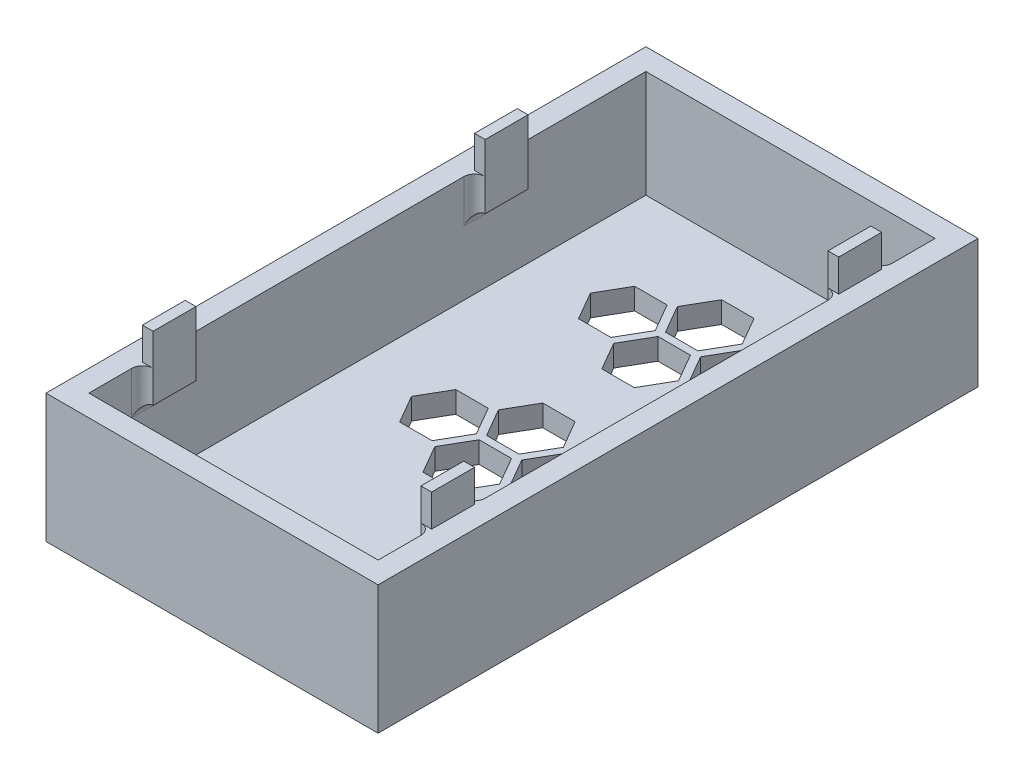
SolidWorks part; units mm, degrees
ref_plane "Plan de face" through (0, 0, 0) normal (0, 0, 1) x (1, 0, 0)
ref_plane "Plan de dessus" through (0, 0, 0) normal (0, 1, 0) x (1, 0, 0)
ref_plane "Plan de droite" through (0, 0, 0) normal (1, 0, 0) x (0, 0, -1)
sketch "Esquisse1" plane through (0, 0, 0) normal (0, 1, 0) x (1, 0, 0)
  line L1 (0, 0) -> (31, 0)
  line L2 (0, 0) -> (0, 56)
  line L3 (0, 56) -> (31, 56)
  line L4 (31, 0) -> (31, 56)
  dimension "D1" = 31
  dimension "D2" = 56
extrude "Boss.-Extru.1" add sketch "Esquisse1" along normal blind 2
sketch "Esquisse2" plane through (0, 2, 0) normal (0, 1, 0) x (1, 0, 0)
  line L0 (16734.8175, -28935.5853) -> (16735.4237, -28935.2353) construction
  line L1 (11.7493, 46.3154) -> (12.3555, 46.6654) construction
  line L2 (13.3806, 43.4899) -> (11.8674, 46.1109)
  line L3 (18.3759, 44.8002) -> (17.7698, 45.1504) construction
  line L4 (15.5, 43.1399) -> (15.5, 43.8399) construction
  line L5 (31, 56) -> (0, 56) construction
  line L6 (13.3806, 26.793) -> (11.8674, 29.4139)
  line L7 (13.2302, 41.8295) -> (12.624, 42.1795) construction
  line L8 (11.8674, 46.1109) -> (8.841, 46.1109)
  line L9 (8.841, 46.1109) -> (7.3278, 43.4899)
  line L10 (7.3278, 43.4899) -> (8.841, 40.869)
  line L11 (8.841, 40.869) -> (11.8674, 40.869)
  line L12 (11.8674, 40.869) -> (13.3806, 43.4899)
  line L13 (18.5264, 46.4609) -> (17.0132, 49.0818)
  line L14 (17.0132, 49.0818) -> (13.9868, 49.0818)
  line L15 (13.9868, 49.0818) -> (12.4736, 46.4609)
  line L16 (12.4736, 46.4609) -> (13.9868, 43.8399)
  line L17 (13.9868, 43.8399) -> (17.0132, 43.8399)
  line L18 (17.0132, 43.8399) -> (18.5264, 46.4609)
  line L19 (18.5264, 40.519) -> (17.0132, 43.1399)
  line L20 (17.0132, 43.1399) -> (13.9868, 43.1399)
  line L21 (13.9868, 43.1399) -> (12.4736, 40.519)
  line L22 (12.4736, 40.519) -> (13.9868, 37.8981)
  line L23 (13.9868, 37.8981) -> (17.0132, 37.8981)
  line L24 (17.0132, 37.8981) -> (18.5264, 40.519)
  line L25 (23.6722, 43.4902) -> (22.1588, 46.111)
  line L26 (22.1588, 46.111) -> (19.1324, 46.1107)
  line L27 (19.1324, 46.1107) -> (17.6194, 43.4897)
  line L28 (17.6194, 43.4897) -> (19.1329, 40.8689)
  line L29 (19.1329, 40.8689) -> (22.1593, 40.8691)
  line L30 (22.1593, 40.8691) -> (23.6722, 43.4902)
  line L31 (17.7698, 41.8295) -> (18.3761, 42.1793) construction
  line L32 (18.3759, 28.1032) -> (17.7698, 28.4534) construction
  line L33 (15.5, 26.443) -> (15.5, 27.143) construction
  line L34 (13.2302, 25.1325) -> (12.624, 25.4825) construction
  line L35 (11.8674, 29.4139) -> (8.841, 29.4139)
  line L36 (8.841, 29.4139) -> (7.3278, 26.793)
  line L37 (7.3278, 26.793) -> (8.841, 24.172)
  line L38 (8.841, 24.172) -> (11.8674, 24.172)
  line L39 (11.8674, 24.172) -> (13.3806, 26.793)
  line L40 (18.5264, 29.7639) -> (17.0132, 32.3848)
  line L41 (17.0132, 32.3848) -> (13.9868, 32.3848)
  line L42 (13.9868, 32.3848) -> (12.4736, 29.7639)
  line L43 (12.4736, 29.7639) -> (13.9868, 27.143)
  line L44 (13.9868, 27.143) -> (17.0132, 27.143)
  line L45 (17.0132, 27.143) -> (18.5264, 29.7639)
  line L46 (18.5264, 23.822) -> (17.0132, 26.443)
  line L47 (17.0132, 26.443) -> (13.9868, 26.443)
  line L48 (13.9868, 26.443) -> (12.4736, 23.822)
  line L49 (12.4736, 23.822) -> (13.9868, 21.2011)
  line L50 (13.9868, 21.2011) -> (17.0132, 21.2011)
  line L51 (17.0132, 21.2011) -> (18.5264, 23.822)
  line L52 (23.6722, 26.7932) -> (22.1588, 29.414)
  line L53 (22.1588, 29.414) -> (19.1324, 29.4138)
  line L54 (19.1324, 29.4138) -> (17.6194, 26.7927)
  line L55 (17.6194, 26.7927) -> (19.1329, 24.1719)
  line L56 (19.1329, 24.1719) -> (22.1593, 24.1722)
  line L57 (22.1593, 24.1722) -> (23.6722, 26.7932)
  line L58 (17.7698, 25.1325) -> (18.3761, 25.4823) construction
  circle A8 centre (10.3542, 43.4899) radius 2.6209 construction
  circle A9 centre (15.5, 46.4609) radius 2.6209 construction
  circle A10 centre (15.5, 40.519) radius 2.6209 construction
  circle A11 centre (20.6458, 43.4899) radius 2.6209 construction
  circle A12 centre (10.3981, 26.7169) radius 2.6209 construction
  circle A13 centre (15.5, 29.7639) radius 2.6209 construction
  circle A14 centre (15.5, 23.822) radius 2.6209 construction
  circle A15 centre (20.6897, 26.7169) radius 2.6209 construction
  point P19 (15.5, 56)
  point P92 (15.5, 32.3848)
  dimension "D1" = 0.7
  dimension "D2" = 0.7
extrude "Enlèv. mat.-Extru.1" cut sketch "Esquisse2" against normal through all
sketch "Esquisse6" plane through (0, 2, 0) normal (0, 1, 0) x (1, 0, 0)
  line L1 (0, 56) -> (31, 56)
  line L2 (0, 56) -> (0, 0)
  line L3 (0, 0) -> (31, 0)
  line L4 (31, 56) -> (31, 0)
  line L5 (2, 54) -> (29, 54)
  line L6 (2, 54) -> (2, 2)
  line L7 (2, 2) -> (29, 2)
  line L8 (29, 54) -> (29, 2)
  dimension "D1" = 2
  dimension "D2" = 2
  dimension "D3" = 2
  dimension "D4" = 2
extrude "Boss.-Extru.3" add sketch "Esquisse6" along normal blind 10
sketch "Esquisse10" plane through (29, 0, 0) normal (-1, 0, 0) x (0, 0, 1)
  line L0 (-54, 12) -> (-54, 2) construction
  line L1 (-49, 15) -> (-45, 15)
  line L2 (-49, 15) -> (-49, 9)
  line L3 (-49, 9) -> (-45, 9)
  line L4 (-45, 15) -> (-45, 9)
  line L6 (-11, 15) -> (-11, 9)
  line L7 (-11, 15) -> (-7, 15)
  line L8 (-7, 15) -> (-7, 9)
  line L9 (-11, 9) -> (-7, 9)
  line L10 (-2, 12) -> (-54, 12) construction
  line L11 (-2, 12) -> (-2, 2) construction
  dimension "D1" = 6
  dimension "D2" = 4
  dimension "D3" = 3
  dimension "D4" = 5
  dimension "D6" = 5
  dimension "D5" = 2
sketch "Esquisse11" plane through (2, 0, 0) normal (1, 0, 0) x (0, 0, -1)
  line L0 (0, 12) -> (56, 12) construction
  line L1 (7, 15) -> (11, 15)
  line L2 (7, 15) -> (7, 9)
  line L3 (7, 9) -> (11, 9)
  line L4 (11, 15) -> (11, 9)
  line L6 (38, 15) -> (42, 15)
  line L7 (38, 15) -> (38, 9)
  line L8 (38, 9) -> (42, 9)
  line L9 (42, 15) -> (42, 9)
  line L11 (54, 12) -> (54, 2) construction
  line L13 (2, 12) -> (2, 2) construction
  dimension "D1" = 3
  dimension "D2" = 4
  dimension "D3" = 6
  dimension "D4" = 12
  dimension "D5" = 6
  dimension "D6" = 4
  dimension "D7" = 3
  dimension "D8" = 5
extrude "Boss.-Extru.8" add sketch "Esquisse10" along normal blind 1
fillet "Congé1" radius 1 6 edges at (29, 9, -9) (29, 10.5, -11) (29, 10.5, -7) (29, 9, -47) (29, 10.5, -45) (29, 10.5, -49)
sketch "Esquisse14" plane through (0, 0, -7) normal (0, 0, 1) x (1, 0, 0)
  line L0 (29, 15) -> (29.8, 14.5)
  line L1 (29.8, 14.5) -> (29.8, 13.5)
  line L2 (29.8, 13.5) -> (29, 13)
  line L3 (29, 12) -> (29, 15) construction
  line L4 (29, 13) -> (29, 15)
  point P3 (29, 14)
  point P8 (29.8, 14)
  dimension "D1" = 0.8
  dimension "D2" = 1
  dimension "D3" = 2
extrude "Boss.-Extru.11" add sketch "Esquisse11" along normal blind 1
fillet "Congé2" radius 1 6 edges at (2, 10.5, -7) (2, 9, -9) (2, 10.5, -11) (2, 10.5, -42) (2, 9, -40) (2, 10.5, -38)
sketch "Esquisse16" plane through (0, 0, -7) normal (0, 0, 1) x (1, 0, 0)
  line L0 (2, 15) -> (1.2, 14.5)
  line L1 (1.2, 14.5) -> (1.2, 13.5)
  line L2 (1.2, 13.5) -> (2, 13)
  line L3 (2, 15) -> (2, 12) construction
  line L4 (2, 13) -> (2, 15)
  point P3 (1.2, 14)
  point P8 (2, 14)
  dimension "D1" = 0.8
  dimension "D2" = 2
  dimension "D3" = 1
